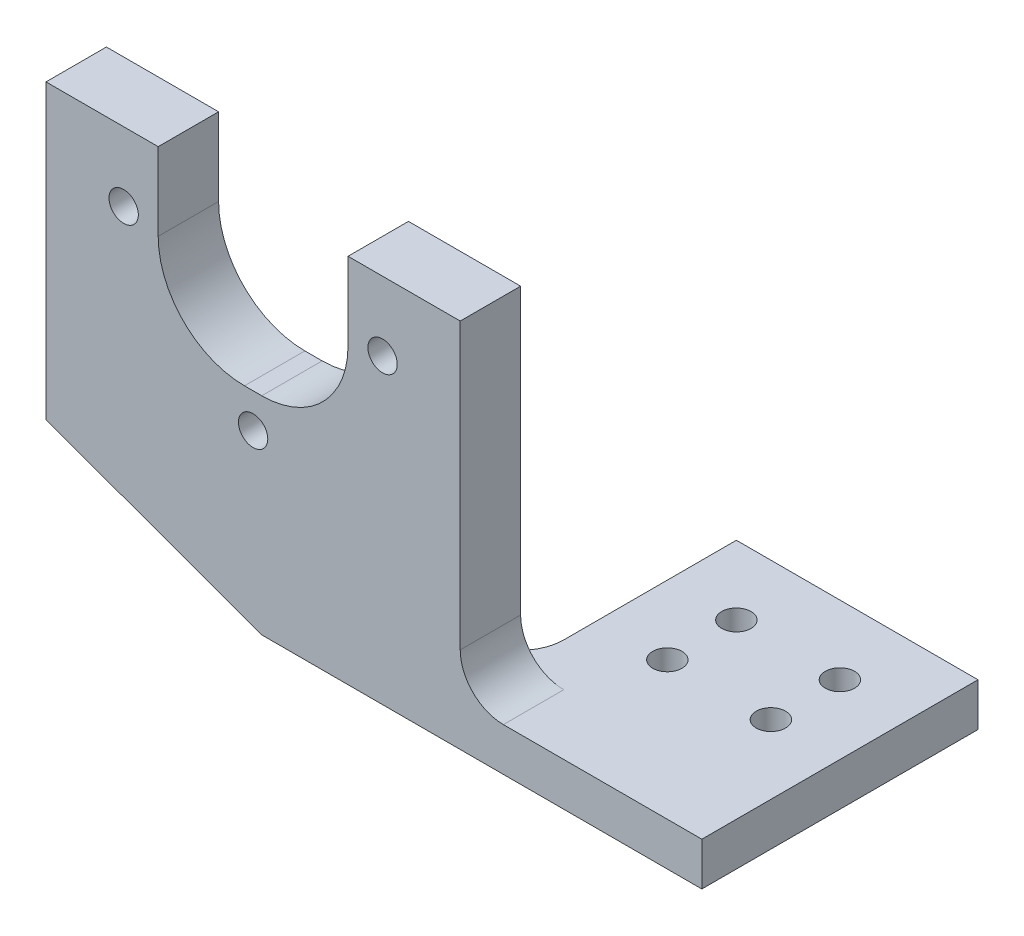
SolidWorks part; units mm, degrees
ref_plane "Front Plane" through (0, 0, 0) normal (0, 0, 1) x (1, 0, 0)
ref_plane "Top Plane" through (0, 0, 0) normal (0, 1, 0) x (1, 0, 0)
ref_plane "Right Plane" through (0, 0, 0) normal (1, 0, 0) x (0, 0, -1)
sketch "Sketch1" plane through (0, 0, 0) normal (0, 1, 0) x (1, 0, 0)
  line L1 (-14, -16) -> (14, -16)
  line L2 (-14, -16) -> (-14, 16)
  line L3 (-14, 16) -> (14, 16)
  line L4 (14, -16) -> (14, 16)
  line L5 (-14, -16) -> (14, 16) construction
  line L6 (-14, 16) -> (14, -16) construction
  point P0 (0, 0)
  dimension "D1" = 32
  dimension "D2" = 28
extrude "Boss-Extrude1" add sketch "Sketch1" along normal blind 5
hole_wizard "M3 Clearance Hole1" positions "Sketch3" profile "Sketch4" hole size "M3" standard "ANSI Metric" end condition through all
sketch "Sketch3" plane through (0, 5, 0) normal (0, 1, 0) x (1, 0, 0)
  line L0 (-14, 16) -> (-14, -16) construction
  line L2 (14, 16) -> (-14, 16) construction
  point P0 (-6, 8)
  point P2 (6, 8)
  point P4 (6, 0)
  point P6 (-6, 0)
  point P13 (13.0597, -5.661)
  point P14 (0, 0)
  dimension "D1" = 8
  dimension "D2" = 12
  dimension "D3" = 8
  dimension "D4" = 8
sketch "Sketch4" plane through (-6, 5, -8) normal (1, 0, 0) x (0, 0, 1)
  line L0 (0, 0) -> (0, 5)
  line L1 (0, 5) -> (1.7, 5)
  line L2 (1.7, 5) -> (1.7, 0)
  line L5 (1.7, 0) -> (0, 0)
  line L11 (0, -6.35) -> (0, 107.95) construction
  dimension "Thru Hole Dia." = 3.4
  dimension "Thru Hole Depth" = 5
sketch "Sketch5" plane through (0, 0, 16) normal (0, 0, 1) x (1, 0, 0)
  line L0 (-14, 0) -> (-62, 0)
  line L1 (-62, 0) -> (-62, 43)
  line L2 (-62, 43) -> (-49, 43)
  line L3 (-49, 43) -> (-49, 24)
  line L4 (-49, 24) -> (-27, 24)
  line L5 (-27, 24) -> (-27, 43)
  line L6 (-27, 43) -> (-14, 43)
  line L9 (-14, 43) -> (-14, 0)
  line L11 (-38, 24) -> (-38, 0) construction
  point P14 (-38, 0)
  dimension "D1" = 22
  dimension "D3" = 43
  dimension "D4" = 19
  dimension "D5" = 24
extrude "Boss-Extrude2" add sketch "Sketch5" against normal blind 7
fillet "Fillet1" radius 10 2 edges at (-27, 24, 12.5) (-49, 24, 12.5)
fillet "Fillet2" radius 5 1 edges at (-14, 5, 12.5)
fillet "Fillet3" radius 5 1 edges at (-14, 2.5, 9)
hole_wizard "M3 Clearance Hole2" positions "Sketch6" profile "Sketch7" hole size "M3" standard "ANSI Metric" end condition through all
sketch "Sketch6" plane through (0, 0, 16) normal (0, 0, 1) x (1, 0, 0)
  line L0 (-62, 0) -> (14, 0) construction
  line L1 (-38, 35) -> (-38, 20) construction
  line L3 (-37, 24) -> (-39, 24) construction
  circle A0 centre (-38, 35) radius 15 construction
  point P0 (-53, 35)
  point P2 (-23, 35)
  point P5 (-38, 20)
  point P29 (-38, 24)
  dimension "D1" = 30
  dimension "D2" = 35
sketch "Sketch7" plane through (-53, 35, 16) normal (1, 0, 0) x (0, -1, 0)
  line L0 (0, 0) -> (0, 32)
  line L1 (0, 32) -> (1.7, 32)
  line L2 (1.7, 32) -> (1.7, 0)
  line L5 (1.7, 0) -> (0, 0)
  line L11 (0, -6.35) -> (0, 107.95) construction
  dimension "Thru Hole Dia." = 3.4
  dimension "Thru Hole Depth" = 32
chamfer "Chamfer1" distance 25 angle 20 1 edges at (-62, 0, 12.5) first distance on face at (-6, 0, -6.3)
